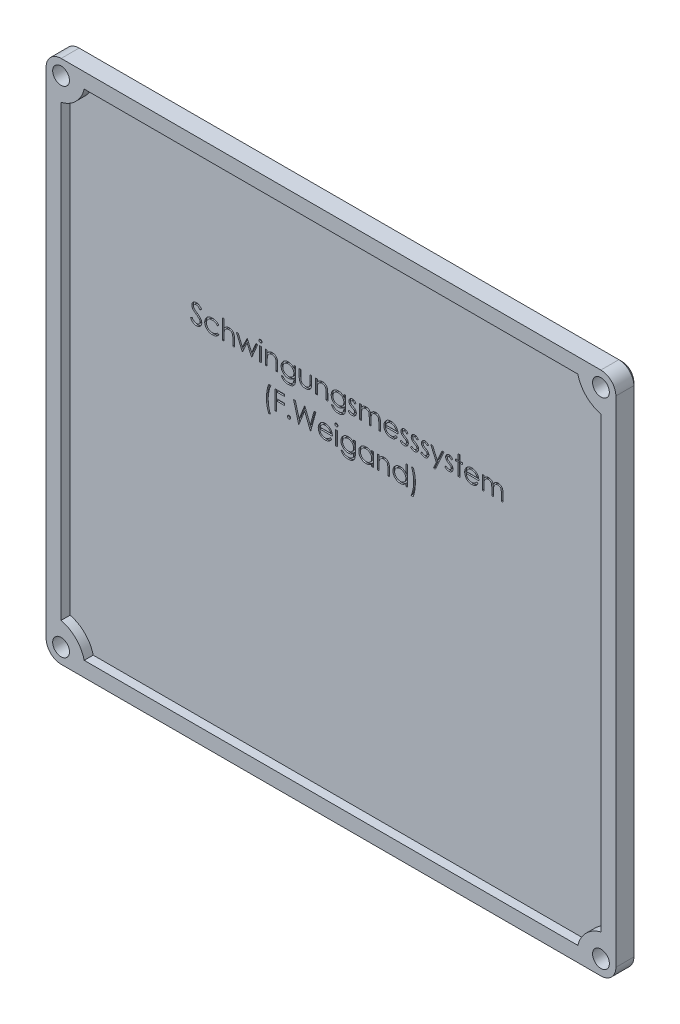
SolidWorks part; units mm, degrees
note: The reader was unsure of these and kept them because the rebuilt part matched: shared geometry of "Skizze1<2>", "Skizze2<5>".
ref_plane "Ebene vorne" through (0, 0, 0) normal (0, 0, 1) x (1, 0, 0)
ref_plane "Ebene oben" through (0, 0, 0) normal (0, 1, 0) x (1, 0, 0)
ref_plane "Ebene rechts" through (0, 0, 0) normal (1, 0, 0) x (0, 0, -1)
sketch "Skizze1" plane through (0, 0, 0) normal (0, 0, 1) x (1, 0, 0)
  line L1 (90, -82.5) -> (-90, -82.5)
  line L2 (90, -82.5) -> (90, 82.5)
  line L3 (90, 82.5) -> (-90, 82.5)
  line L4 (-90, -82.5) -> (-90, 82.5)
  line L5 (90, -82.5) -> (-90, 82.5) construction
  line L6 (90, 82.5) -> (-90, -82.5) construction
  line L7 (95, -87.5) -> (-95, -87.5)
  line L8 (95, -87.5) -> (95, 87.5)
  line L9 (95, 87.5) -> (-95, 87.5)
  line L10 (-95, -87.5) -> (-95, 87.5)
  line L11 (95, -87.5) -> (-95, 87.5) construction
  line L12 (95, 87.5) -> (-95, -87.5) construction
  point P0 (0, 0)
  point P5 (0, 0)
  dimension "D1" = 5
  dimension "D2" = 5
  dimension "D3" = 180
  dimension "D4" = 165
extrude "Aufsatz-Linear austragen1" add sketch "Skizze1" along normal blind 3
extrude "Aufsatz-Linear austragen2" add sketch "Skizze1<2>" against normal blind 4 contours L9 L10 L7 L8
sketch "Skizze1<2>" plane through (0, 0, 0) normal (0, 0, 1) x (1, 0, 0) same geometry as "Skizze1"
sketch "Skizze2" plane through (0, 0, 3) normal (0, 0, 1) x (1, 0, 0)
  line L0 (-92.5, 85) -> (-92.5, 74.5)
  line L1 (-92.5, 85) -> (-82, 85)
  line L2 (-92.5, 85) -> (-85.0754, 77.5754) construction
  line L3 (-95, 87.5) -> (-90, 82.5) construction
  line L4 (0, 9.9788) -> (0, -13.3423) construction
  line L5 (-10.3406, 0) -> (19.0775, 0) construction
  line L6 (92.5, 85) -> (92.5, 74.5)
  line L7 (92.5, 85) -> (82, 85)
  line L8 (92.5, -85) -> (82, -85)
  line L9 (92.5, -85) -> (92.5, -74.5)
  line L10 (-92.5, -85) -> (-92.5, -74.5)
  line L11 (-92.5, -85) -> (-82, -85)
  arc A0 (-92.5, 74.5) -> (-82, 85) centre (-92.5, 85) ccw
  circle A1 centre (-90.0251, 82.5251) radius 2.8
  arc A2 (92.5, 74.5) -> (82, 85) centre (92.5, 85) cw
  circle A3 centre (90.0251, 82.5251) radius 2.8
  arc A4 (92.5, -74.5) -> (82, -85) centre (92.5, -85) ccw
  circle A5 centre (90.0251, -82.5251) radius 2.8
  circle A6 centre (-90.0251, -82.5251) radius 2.8
  arc A7 (-92.5, -74.5) -> (-82, -85) centre (-92.5, -85) cw
  dimension "D1" = 7
  dimension "D2" = 10.5
  dimension "D3" = 5.6
extrude "Schnitt-Linear austragen2" cut sketch "Skizze2" against normal through all contours A1 | A3 | A5 | A6
fillet "Verrundung1" radius 5 4 edges at (-95, -87.5, -0.5) (95, -87.5, -0.5) (95, 87.5, -0.5) (-95, 87.5, -0.5)
chamfer "Fase1" distance 1 angle 45 8 edges at (93.5355, -86.0355, -4) (95, 0, -4) (93.5355, 86.0355, -4) (0, 87.5, -4) (-93.5355, 86.0355, -4) (-95, 0, -4) (-93.5355, -86.0355, -4) (0, -87.5, -4)
extrude "Aufsatz-Linear austragen3" add sketch "Skizze2<5>" against normal up to surface (3 mm away)
sketch "Skizze2<5>" plane through (0, 0, 3) normal (0, 0, 1) x (1, 0, 0) same geometry as "Skizze2"
sketch "Skizze3" plane through (0, 0, 0) normal (0, 0, 1) x (1, 0, 0)
  text T0 "Schwingungsmesssystem\r\n          (F.Weigand)" font "Century Gothic" height in points 24
  dimension "D1" = 50
  dimension "D2" = 30
extrude "Schnitt-Linear austragen3" cut sketch "Skizze3" against normal blind 0.5
equation "\"D2@Skizze1\"=\"D1@Skizze1\""
